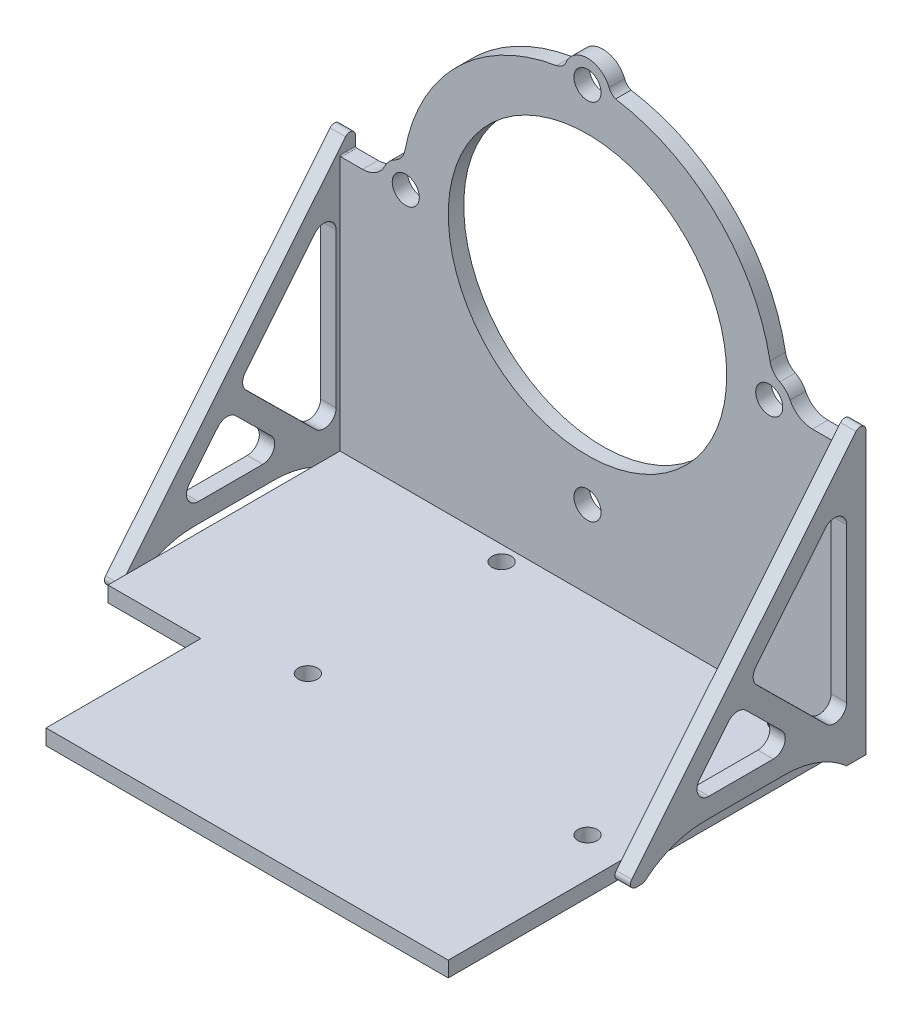
SolidWorks part; units mm, degrees
ref_plane "Front Plane" through (0, 0, 0) normal (0, 0, 1) x (1, 0, 0)
ref_plane "Top Plane" through (0, 0, 0) normal (0, 1, 0) x (1, 0, 0)
ref_plane "Right Plane" through (0, 0, 0) normal (1, 0, 0) x (0, 0, -1)
sketch "Sketch2" plane through (0, 0, 0) normal (0, 1, 0) x (1, 0, 0)
  line L0 (0, 0) -> (0, -101.6)
  line L1 (0, -101.6) -> (38.1, -101.6)
  line L2 (38.1, -101.6) -> (38.1, -165.1)
  line L3 (38.1, -165.1) -> (203.2, -165.1)
  line L4 (203.2, -165.1) -> (203.2, 0)
  line L5 (203.2, 0) -> (0, 0)
  dimension "D1" = 165.1
  dimension "D2" = 165.1
  dimension "D3" = 63.5
  dimension "D4" = 38.1
extrude "Boss-Extrude1" add sketch "Sketch2" along normal blind 6.35
sketch "Sketch3" plane through (0, 0, 0) normal (0, 0, 1) x (1, 0, 0)
  line L0 (203.2, 6.35) -> (203.2, 196.85)
  line L1 (203.2, 196.85) -> (0, 196.85)
  line L2 (0, 196.85) -> (0, 6.35)
  line L3 (0, 6.35) -> (203.2, 6.35)
  dimension "D1" = 190.5
extrude "Boss-Extrude2" add sketch "Sketch3" along normal blind 6.35
sketch "Sketch4" plane through (0, 0, 6.35) normal (0, 0, 1) x (1, 0, 0)
  line L0 (0, 6.35) -> (101.6, 6.35) construction
  line L1 (38.1, 6.35) -> (203.2, 6.35) construction
  line L2 (101.6, 6.35) -> (101.6, 112.7125) construction
  circle A0 centre (101.6, 112.7125) radius 57.15
  dimension "D3" = 114.3
  dimension "D1" = 101.6
  dimension "D2" = 106.3625
extrude "Cut-Extrude1" cut sketch "Sketch4" against normal blind 6.35
sketch "Sketch5" plane through (0, 0, 0) normal (0, 0, -1) x (-1, 0, 0)
  line L0 (0, 6.35) -> (-203.2, 6.35) construction
  line L1 (-101.6, 6.35) -> (-101.6, 38.1125) construction
  circle A0 centre (-101.6, 38.1125) radius 5.5563
  circle A1 centre (-101.6, 112.7125) radius 74.6 construction
  circle A2 centre (-101.6, 187.3125) radius 5.5563
  circle A3 centre (-27, 112.7125) radius 5.5562
  circle A4 centre (-176.2, 112.7125) radius 5.5563
  point P16 (-26.9875, 112.7125)
  dimension "D2" = 11.1125
  dimension "D1" = 149.2
extrude "Cut-Extrude2" cut sketch "Sketch5" against normal blind 6.35
sketch "Sketch6" plane through (0, 0, 0) normal (0, 0, -1) x (-1, 0, 0)
  line L0 (-44.45, 112.7125) -> (-25.4, 112.7125) construction
  line L1 (0, 0) -> (0, 111.125) construction
  line L2 (0, 196.85) -> (0, 0) construction
  line L3 (0, 111.125) -> (-203.2, 111.125) construction
  line L4 (-203.2, 196.85) -> (-203.2, 0) construction
  line L5 (0, 111.125) -> (-9.2796, 111.125)
  line L6 (-88.3893, 190.809) -> (-114.449, 190.809) construction
  line L7 (-7.9098, 126.5834) -> (-186.0002, 126.5834) construction
  line L8 (-20.9502, 121.1891) -> (-193.0529, 121.1891) construction
  line L9 (-203.2, 111.125) -> (-193.9204, 111.125)
  line L10 (-203.2, 111.125) -> (-224.6051, 111.125)
  line L11 (-224.6051, 111.125) -> (-224.6051, 212.9952)
  line L12 (-224.6051, 212.9952) -> (24.4438, 212.9952)
  line L13 (24.4438, 212.9952) -> (24.4438, 111.125)
  line L14 (24.4438, 111.125) -> (0, 111.125)
  circle A0 centre (-101.6, 112.7125) radius 76.2 construction
  circle A1 centre (-101.6, 112.7125) radius 57.15 construction
  circle A2 centre (-101.6, 187.3125) radius 9.525 construction
  circle A3 centre (-27, 112.7125) radius 9.525 construction
  circle A4 centre (-176.2, 112.7125) radius 9.525 construction
  arc A5 (-9.2796, 111.125) -> (-18.4256, 116.8605) centre (-9.2796, 121.285) cw
  arc A6 (-18.4256, 116.8605) -> (-22.6558, 121.1891) centre (-27, 112.7125) ccw
  arc A7 (-22.6558, 121.1891) -> (-26.6731, 126.5834) centre (-19.1804, 127.9705) cw
  arc A8 (-26.6731, 126.5834) -> (-88.9376, 187.8531) centre (-101.6, 112.7125) ccw
  arc A9 (-88.9376, 187.8531) -> (-92.74, 190.809) centre (-88.0935, 192.8624) cw
  arc A10 (-92.74, 190.809) -> (-110.46, 190.809) centre (-101.6, 187.3125) ccw
  arc A11 (-110.46, 190.809) -> (-113.1063, 188.0388) centre (-115.1854, 192.6738) cw
  arc A12 (-113.1063, 188.0388) -> (-176.5269, 126.5834) centre (-101.6, 112.7125) ccw
  arc A13 (-176.5269, 126.5834) -> (-180.5442, 121.1891) centre (-184.0196, 127.9705) cw
  arc A14 (-193.9204, 111.125) -> (-184.7744, 116.8605) centre (-193.9204, 121.285) ccw
  arc A15 (-184.7744, 116.8605) -> (-180.5442, 121.1891) centre (-176.2, 112.7125) cw
  dimension "D1" = 19.05
  dimension "D2" = 19.05
  dimension "D7" = 5.08
  dimension "D8" = 2.6463
  dimension "D10" = 10.16
  dimension "D9" = 7.62
  dimension "D11" = 5.08
  dimension "D12" = 7.62
  dimension "D13" = 10.16
  dimension "D3" = 111.125
  dimension "D5" = 249.0489
  dimension "D6" = 21.4051
extrude "Cut-Extrude3" cut sketch "Sketch6" against normal blind 6.35
sketch "Sketch7" plane through (0, 6.35, 0) normal (0, 1, 0) x (1, 0, 0)
  line L0 (203.2, -92.05) -> (187.325, -92.05) construction
  line L1 (203.2, -165.1) -> (203.2, -6.35) construction
  line L2 (0, -6.35) -> (203.2, -6.35) construction
  line L3 (187.325, -92.05) -> (187.325, -6.35) construction
  line L4 (187.325, -12.55) -> (203.2, -12.55) construction
  line L5 (72.525, -12.55) -> (72.525, -92.05) construction
  circle A0 centre (187.325, -92.05) radius 3.9687
  circle A1 centre (187.325, -12.55) radius 3.9687
  circle A2 centre (72.525, -12.55) radius 3.9688
  circle A3 centre (72.525, -92.05) radius 3.9687
  dimension "D3" = 7.9375
  dimension "D1" = 15.875
  dimension "D2" = 85.7
  dimension "D4" = 79.5
  dimension "D5" = 114.8
extrude "Cut-Extrude4" cut sketch "Sketch7" against normal blind 6.35
sketch "Sketch8" plane through (0, 0, 0) normal (1, 0, 0) x (0, 0, -1)
  line L0 (0, 0) -> (-99.2187, 0)
  line L1 (-165.1, 0) -> (0, 0) construction
  line L2 (-99.2187, 0) -> (0, 121.92)
  line L3 (0, 111.125) -> (0, 0) construction
  line L4 (0, 121.92) -> (0, 0)
  dimension "D1" = 121.92
  dimension "D2" = 99.2188
extrude "Boss-Extrude3" add sketch "Sketch8" against normal blind 6.35
sketch "Sketch10" plane through (203.2, 0, 0) normal (1, 0, 0) x (0, 0, -1)
  line L0 (-99.2188, 0) -> (0, 0)
  line L1 (0, 0) -> (0, 121.92)
  line L2 (0, 111.125) -> (0, 0) construction
  line L3 (0, 121.92) -> (-99.2188, 0)
  dimension "D1" = 121.92
  dimension "D2" = 99.2188
extrude "Boss-Extrude4" add sketch "Sketch10" along normal blind 6.35
sketch "Sketch11" plane through (209.55, 0, 0) normal (1, 0, 0) x (0, 0, -1)
  line L1 (-7.9375, 0) -> (-91.2813, 0)
  line L2 (-99.2188, 0) -> (0, 0) construction
  line L3 (-66.0805, 9.525) -> (-33.1383, 9.525)
  arc A0 (-91.2813, 0) -> (-66.0805, 9.525) centre (-66.0805, -28.575) cw
  arc A1 (-33.1383, 9.525) -> (-7.9375, 0) centre (-33.1383, -28.575) cw
  dimension "D4" = 38.1
  dimension "D5" = 38.1
  dimension "D1" = 7.9375
  dimension "D2" = 7.9375
  dimension "D3" = 9.525
extrude "Cut-Extrude5" cut sketch "Sketch11" against normal up to surface (6.35 mm away) contours L1 A0 L3 A1 up to face at (203.2, 3.175, 130.8675)
sketch "Sketch12" plane through (-6.35, 0, 0) normal (-1, 0, 0) x (0, 0, 1)
  line L0 (91.2813, 0) -> (7.9375, 0)
  line L1 (33.1383, 9.525) -> (66.0805, 9.525)
  line L2 (99.2187, 0) -> (0, 0) construction
  arc A0 (7.9375, 0) -> (33.1383, 9.525) centre (33.1383, -28.575) cw
  arc A1 (66.0805, 9.525) -> (91.2813, 0) centre (66.0805, -28.575) cw
  dimension "D1" = 38.1
  dimension "D2" = 38.1
  dimension "D3" = 7.9375
  dimension "D4" = 9.525
  dimension "D5" = 7.9375
extrude "Cut-Extrude6" cut sketch "Sketch12" against normal up to surface (6.35 mm away) up to face at (0, 3.175, 99.1175)
sketch "Sketch13" plane through (209.55, 0, 0) normal (1, 0, 0) x (0, 0, -1)
  line L0 (-7.9375, 99.5912) -> (-7.9375, 10.6912)
  line L1 (0, 0) -> (0, 121.92) construction
  line L2 (-7.9375, 99.5912) -> (-48.0187, 50.3393)
  line L3 (0, 121.92) -> (-99.2188, 0) construction
  line L4 (-48.0187, 50.3393) -> (-7.9375, 10.6912)
  line L5 (-24.1458, 79.6745) -> (-79.515, 11.6368) construction
  line L6 (0, 121.92) -> (-11.0085, 121.92) construction
  line L7 (-89.376, 17.4625) -> (3.2132, 17.4625) construction
  line L8 (-66.0805, 9.525) -> (-33.1383, 9.525) construction
  line L9 (-53.8667, 44.9593) -> (-22.964, 14.3904) construction
  line L10 (-53.0525, 44.1538) -> (-26.0696, 17.4625)
  line L11 (-53.0525, 44.1538) -> (-74.774, 17.4625)
  line L12 (-26.0696, 17.4625) -> (-74.774, 17.4625)
  point P10 (-48.0187, 50.3393)
  point P18 (-7.9375, 10.6912)
  point P21 (-7.9375, 99.5912)
  dimension "D5" = 7.9375
  dimension "D1" = 7.9375
  dimension "D2" = 7.9375
  dimension "D3" = 88.9
  dimension "D4" = 63.5
  dimension "D6" = 7.9375
extrude "Cut-Extrude7" cut sketch "Sketch13" against normal through all contours L11 L12 L10 | L0 L4 L2
fillet "Fillet1" radius 4.92 12 edges at (206.375, 99.5912, 7.9375) (206.375, 17.4625, 26.0696) (206.375, 17.4625, 74.774) (206.375, 44.1538, 53.0525) (206.375, 50.3393, 48.0187) (206.375, 10.6912, 7.9375) (-3.175, 17.4625, 26.0696) (-3.175, 17.4625, 74.774) (-3.175, 44.1538, 53.0525) (-3.175, 50.3393, 48.0187) (-3.175, 10.6912, 7.9375) (-3.175, 99.5912, 7.9375)
fillet "Fillet4" radius 2.286 6 edges at (-3.175, 121.92, 0) (206.375, 121.92, 0) (206.375, 0, 91.2812) (206.375, 0, 99.2187) (-3.175, 0, 91.2813) (-3.175, 0, 99.2187)
fillet "Fillet6" radius 0.508 1 edges at (0, 111.125, 3.175)
